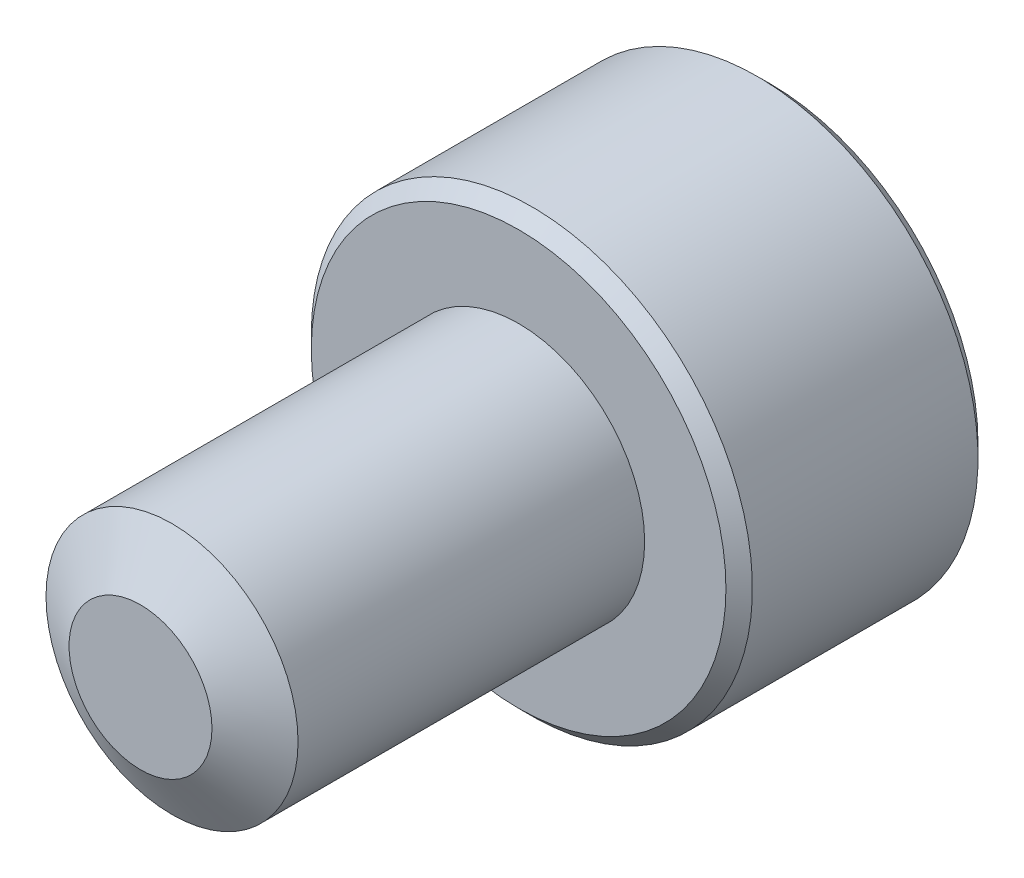
SolidWorks part; units mm, degrees
ref_plane "Front Plane" through (0, 0, 0) normal (0, 0, 1) x (1, 0, 0)
ref_plane "Top Plane" through (0, 0, 0) normal (0, 1, 0) x (1, 0, 0)
ref_plane "Right Plane" through (0, 0, 0) normal (1, 0, 0) x (0, 0, -1)
sketch "Sketch1" plane through (0, 0, 0) normal (0, 0, 1) x (1, 0, 0)
  circle A0 centre (0, 0) radius 2
  dimension "OD" = 4
extrude "Extrude1" add sketch "Sketch1" against normal blind 6
sketch "Sketch2" plane through (0, 0, 0) normal (0, 0, 1) x (1, 0, 0)
  circle A0 centre (0, 0) radius 2 construction
  circle A1 centre (0, 0) radius 2
curve "Helix/Spiral1" pitch 0.7 height 6.7 radius 2 centre (0, 0, 0) axis (0, 0, -1) start towards (0, 1, 0) parameters "pitch"=0.7
sketch "Sketch3" plane through (0, 0, 0) normal (1, 0, 0) x (0, 0, -1)
  line L0 (-0.6125, 2) -> (-0.35, 1.5453)
  line L1 (-0.35, 1.5453) -> (-0.2625, 1.5453)
  line L2 (-0.2625, 1.5453) -> (0, 2)
  line L3 (-0.6125, 2) -> (0, 2)
  line L4 (-0.3063, 2) -> (-0.3063, 1.5453) construction
  line L5 (-0.4813, 1.7727) -> (-0.1313, 1.7727) construction
  line L6 (0, 2) -> (0, -2) construction
  line L7 (0, -2) -> (6, -2) construction
  point P11 (3.15, -2)
  dimension "D1" = 0.0875
  dimension "D2" = 0.35
  dimension "D3" = 60
  dimension "D4" = 3.15
sweep "Cut-Sweep1" cut profiles "Sketch3" path "Helix/Spiral1" align with end faces yes
sketch "Sketch4" plane through (0, 0, 0) normal (1, 0, 0) x (0, 0, -1)
  line L0 (0.4962, 2) -> (0, 1.2913)
  line L1 (0, 1.2913) -> (0, 2)
  line L2 (0.4962, 2) -> (0, 2)
  line L3 (-0.6125, 2) -> (0, 2) construction
  line L4 (0, 0) -> (7.0209, 0) construction
  dimension "D1" = 55
  dimension "D2" = 0.254
revolve "Cut-Revolve1" cut sketch "Sketch4" angle 360 about L4
sketch "Sketch5" plane through (0, 0, 0) normal (1, 0, 0) x (0, 0, -1)
  line L0 (6, -1.8828) -> (6, 1.3901) construction
  line L1 (6, 2) -> (0.1203, 2)
  line L2 (6, 2) -> (6, 0)
  line L3 (6, 0) -> (0.0001, 0)
  line L4 (0.0001, 1.6698) -> (0.0001, 0)
  line L5 (0.1203, 2) -> (0.0001, 1.6698)
  line L6 (0, 0) -> (9.9695, 0) construction
  point P3 (0.0001, 2)
  point P10 (0.0001, 2)
  dimension "D1" = 0.3302
  dimension "Thread min" = 0.0001
  dimension "D3" = 20
revolve "partially thread" [suppressed] add sketch "Sketch5" angle 360 about L6
sketch "Sketch6" plane through (0, 0, -6) normal (0, 0, -1) x (-1, 0, 0)
  circle A0 centre (0, 0) radius 3.5
  dimension "head dia" = 7
extrude "Extrude2" add sketch "Sketch6" along normal blind 4
sketch "Sketch7" plane through (0, 0, -10) normal (0, 0, -1) x (-1, 0, 0)
  line L1 (0, 1.7321) -> (-1.5, 0.866)
  line L2 (-1.5, 0.866) -> (-1.5, -0.866)
  line L3 (-1.5, -0.866) -> (0, -1.7321)
  line L4 (0, -1.7321) -> (1.5, -0.866)
  line L5 (1.5, -0.866) -> (1.5, 0.866)
  line L6 (1.5, 0.866) -> (0, 1.7321)
  circle A0 centre (0, 0) radius 1.5 construction
  dimension "hex dia" = 3
extrude "Cut-Extrude1" cut sketch "Sketch7" against normal blind 2.25
sketch "Sketch8" plane through (0, 0, -10) normal (0, 0, -1) x (-1, 0, 0)
  circle A0 centre (0, 0) radius 1.7321
extrude "Cut-Extrude2" cut sketch "Sketch8" against normal through all draft 45
chamfer "Chamfer1" distance 0.21 angle 45 2 edges at (-3.5, 0, -10) (-3.5, 0, -6)
sketch "Sketch9" plane through (0, 0, 0) normal (1, 0, 0) x (0, 0, -1)
  line L0 (0, 2) -> (0, -2) construction
  line L1 (3.85, 2) -> (3.85, -2) construction
  dimension "D1" = 3.85
sketch "Sketch10" plane through (0, 0, 0) normal (1, 0, 0) x (0, 0, -1)
  line L0 (6, 2) -> (6, 0)
  line L1 (6, 2) -> (5.825, 2)
  line L2 (5.825, 2) -> (4.9966, 0)
  line L3 (6, 0) -> (4.9966, 0)
  line L4 (6, 3.29) -> (6, -3.29) construction
  dimension "D1" = 22.5
  dimension "D2" = 0.175
revolve "Revolve1" add sketch "Sketch10" angle 360 about L3
sketch "Sketch12" plane through (0, 0, 0) normal (0, 0, 1) x (1, 0, 0)
  circle A0 centre (0, 0) radius 2
  dimension "D1" = 4
extrude "Boss-Extrude1" add sketch "Sketch12" against normal up to surface (6 mm away) up to face at (-3.29, 0, -6)
chamfer "Chamfer2" distance 0.5 angle 60 1 edges at (2, 0, 0) first distance on face at (2, 0, -6)
equation "\"D3@Helix/Spiral1\" = \"screw length@Extrude1\"+\"pitch@Helix/Spiral1\""
equation "\"D1@Sketch3\" = \"pitch@Helix/Spiral1\"*.125"
equation "\"D2@Sketch3\" = \"pitch@Helix/Spiral1\"*.5"
equation "\"D1@Cut-Extrude1\" = \"hex dia@Sketch7\"*.75"
equation "\"D1@Chamfer1\" = \"head dia@Sketch6\"*.03"
equation "\"D1@Sketch9\" = \"pitch@Helix/Spiral1\"*5.5"
equation "\"D2@Sketch10\" = \"pitch@Helix/Spiral1\"*.25"
equation "\"D4@Sketch3\" = \"pitch@Helix/Spiral1\"*4.50"
